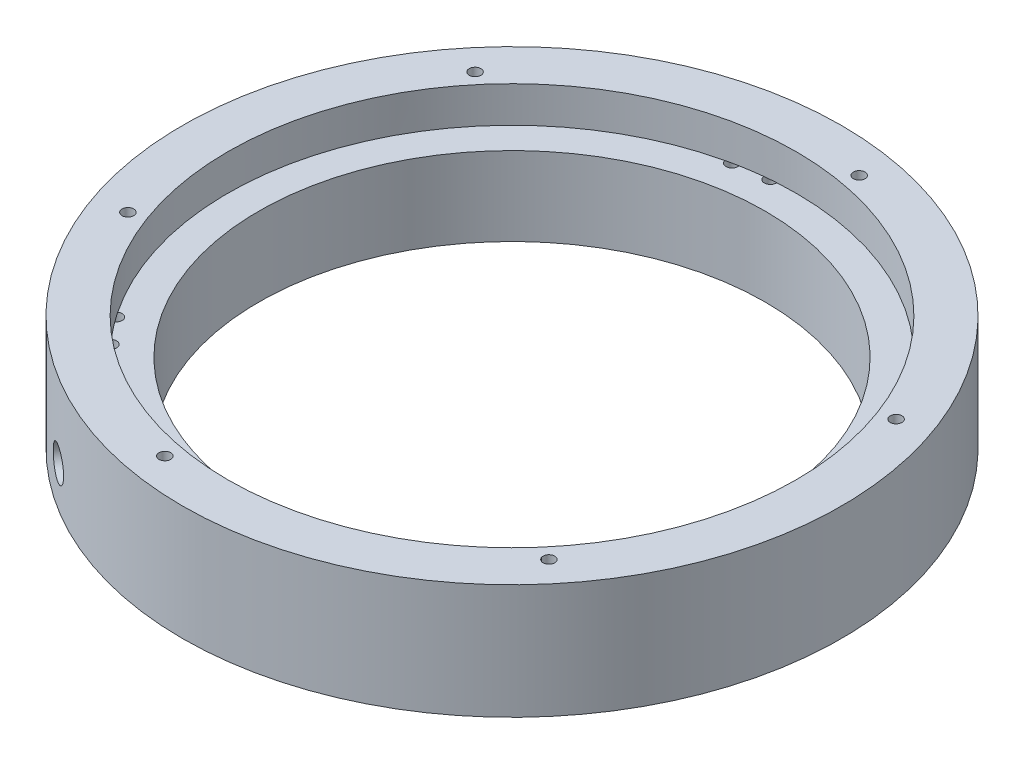
SolidWorks part; units mm, degrees
material "6061 Alloy"
ref_plane "Front Plane" through (0, 0, 0) normal (0, 0, 1) x (1, 0, 0)
ref_plane "Top Plane" through (0, 0, 0) normal (0, 1, 0) x (1, 0, 0)
ref_plane "Right Plane" through (0, 0, 0) normal (1, 0, 0) x (0, 0, -1)
sketch "Sketch1" plane through (0, 0, 0) normal (0, 1, 0) x (1, 0, 0)
  line L0 (26.7963, -63.1282) -> (0, 0) construction
  line L1 (0, 0) -> (0, -32.7983) construction
  line L2 (0, 0) -> (58.126, -27.1046) construction
  line L3 (0, 0) -> (-15.1655, -86.0079) construction
  line L4 (0, 0) -> (84.7676, -52.9687) construction
  circle A0 centre (0, 0) radius 57.15
  circle A1 centre (0, 0) radius 74.3712
  circle A3 centre (0, 0) radius 64.135
  circle A4 centre (-11.7434, -66.6001) radius 1.3208
  circle A5 centre (26.7963, -63.1282) radius 1.9939
  circle A6 centre (26.7963, -63.1282) radius 5.3277
  circle A7 centre (58.126, -27.1046) radius 1.3589
  circle A8 centre (60.9305, -20.0194) radius 1.3589
  dimension "D1" = 114.3
  dimension "D5" = 2.6416
  dimension "D7" = 3.9878
  dimension "D9" = 10.6553
  dimension "D10" = 2.7178
  dimension "D2" = 148.7424
  dimension "D4" = 67.6275
  dimension "D6" = 68.58
  dimension "D8" = 23
  dimension "D11" = 65
  dimension "D15" = 58
  dimension "D12" = 7.62
  dimension "D13" = 10
  dimension "D3" = 6.985
extrude "Boss-Extrude1" add sketch "Sketch1" along normal blind 17.78 contours A7 A3 A6 A0 | A3 A6 A5 | A5 | A3 A6 | A1 A7 A3 A6 A4 | A3 A7 | A3 A7 | A3 A8 | A3 A8 region at (-72.2677, 0, 0) region at (61.6385, 0, 9.1979) region at (24.9157, 0, 58.6977) region at (25.1182, 0, 59.1748) region at (61.4759, 0, 20.1987) region at (60.3801, 0, 19.8386) region at (57.601, 0, 26.8598) region at (58.6464, 0, 27.3473) region at (26.7963, 0, 63.1282)
extrude "Boss-Extrude3" add sketch "Sketch1<3>" along normal blind 8.128 from surface contours A1 A7 A3 A6 A4 | A3 A6 A5 | A5 | A3 A7 | A3 A8 region at (-72.2677, 0, 0) region at (25.1182, 0, 59.1748) region at (61.4759, 0, 20.1987) region at (58.6464, 0, 27.3473) region at (26.7963, 0, 63.1282) starting at face at (0, 17.78, 57.15)
sketch "Sketch1<3>" plane through (0, 0, 0) normal (0, 1, 0) x (1, 0, 0) same geometry as "Sketch1"
pattern_circular "CirPattern1" count 6 over 360 about axis through (0, 25.908, 0) along (0, 1, 0) of face at (-11.7434, 0, 67.9209)
sketch "Sketch2" plane through (0, 0, 0) normal (1, 0, 0) x (0, 0, -1)
  line L0 (-57.15, 0) -> (57.15, 0) construction
  line L1 (57.15, 17.78) -> (-57.15, 17.78) construction
  line L2 (-57.15, 0) -> (57.15, 0)
  line L3 (57.15, 17.78) -> (-57.15, 17.78)
  line L4 (91.6697, 17.018) -> (97.1828, 17.018) construction
  line L5 (0, 17.78) -> (0, 35.8369)
  circle A0 centre (60.6425, 18.6055) radius 1.5875 construction
  circle A1 centre (60.6425, 18.669) radius 1.651
  dimension "D2" = 3.175
  dimension "D4" = 3.302
  dimension "D1" = 60.6425
  dimension "D3" = 0.762
extrude "Cut-Extrude2" cut sketch "Sketch1<4>" along normal blind 5.08 contours A3 A6 A5 | A3 A6 | A6 region at (24.9157, 0, 58.6977) region at (25.1182, 0, 59.1748)
sketch "Sketch1<4>" plane through (0, 0, 0) normal (0, 1, 0) x (1, 0, 0) same geometry as "Sketch1"
extrude "Cut-Extrude3" cut sketch "Sketch1<5>" along normal blind 17.78 contours A5 region at (26.7963, 0, 63.1282)
sketch "Sketch1<5>" plane through (0, 0, 0) normal (0, 1, 0) x (1, 0, 0) same geometry as "Sketch1"
pattern_circular "CirPattern3" count 3 over 360 about axis through (0, 0, 0) along (0, 1, 0) of face at (26.7963, 17.78, 65.1221) of face at (26.7963, 17.78, 65.1221) of face at (26.7963, 5.08, 65.1221) of face at (26.7963, 5.08, 68.4559)
ref_plane "Plane1" through (0, 0, 0) normal (-0.5299, 0, 0.848) x (0.848, 0, 0.5299)
sketch "Sketch3" plane through (0, 0, 0) normal (-0.5299, 0, 0.848) x (0.848, 0, 0.5299)
  line L0 (57.15, 17.78) -> (-57.15, 17.78) construction
  line L1 (57.15, 17.78) -> (-57.15, 17.78)
  line L2 (0, 0) -> (0, 17.78) construction
  circle A0 centre (0, 8.89) radius 3.6576
  circle A1 centre (0, 8.89) radius 3.9751
  dimension "D1" = 7.3152
  dimension "D3" = 7.9502
  dimension "D2" = 8.89
extrude "Cut-Extrude5" cut sketch "Sketch3" along normal up to surface (74.2812 mm away) contours L2 A0 | A0 L2 region at (-1.3165, 8.89, -0.8226) region at (1.3165, 8.89, 0.8226) up to face at (0, 0, 74.3712)
extrude "Cut-Extrude13" cut sketch "Sketch1<6>" along normal up to surface (17.78 mm away) contours A3 A8 | A3 A8 | A7 region at (61.4759, 0, 20.1987) region at (60.3801, 0, 19.8386) up to face at (0, 17.78, 57.15)
sketch "Sketch1<6>" plane through (0, 0, 0) normal (0, 1, 0) x (1, 0, 0) same geometry as "Sketch1"
pattern_circular "CirPattern4" count 3 over 360 about axis through (0, 0, 0) along (0, 1, 0) of "Cut-Extrude13"
equation "\"Middle Coupler Inner Daimeter\"= 3.875in"
equation "\"Middle Coupler  Wall Thickness\" = 0.25in"
equation "\"Middle Coupler Bottom Thickness\"= 0.2in"
equation "\"Bearing Rail Offset\"= 0.45in"
equation "\"3-56 UNF Tap\"= 0.089in"
equation "\"3-56 UNF Clearance\"= 0.104in"
equation "\"Ball Bearing Distance\"= 0.03in"
equation "\"D1@Sketch1\"=\"Middle Coupler Inner Daimeter\"+0.625in"
equation "\"D3@Sketch1\"=0.275"
equation "\"D4@Sketch1\"=\"Middle Coupler Inner Daimeter\"/2+0.625/2+0.275+0.275/2"
equation "\"D5@Sketch1\"=\"3-48 Clearance\""
equation "\"D1@Sketch2\"=\"Middle Coupler Inner Daimeter\"/2in + \"Bearing Rail Offset\""
equation "\"D3@Sketch2\"=\"Ball Bearing Distance\""
equation "\"D4@Sketch2\"=\"D2@Sketch2\"+0.005"
equation "\"D1@Boss-Extrude3\"=0.3 + 0.01*2"
equation "\"TCA Outer Diameter\" = 6in"
equation "\"Interstage Aeroframe Wall Thickness\" = 0.072in"
equation "\"Compression Spring OD\"= 0.42in"
equation "\"10-24 Tap\"= 0.157in"
equation "\"10-24 Clearance\"= 0.196in"
equation "\"Lower Stage Fuselage Wall Thickness\" = 0.25in"
equation "\"6-32 Tap\" = 0.107in"
equation "\"D10@Sketch1\"=\"6-32 Tap\""
equation "\"1/4-20 Tap\" = 0.201in"
equation "\"D1@Sketch3\"=0.176 + 0.056*2"
equation "\"12-24 Tap\" = 0.177in"
equation "\"D3@Sketch3\"=0.313"
equation "\"3-48 Tap\"= 0.079in"
equation "\"3-48 Clearance\" = 0.104in"
equation "\"6-32 Clearance\" = 0.144"
equation "\"D2@Sketch1\"=\"TCA Outer Diameter\"-\"Interstage Aeroframe Wall Thickness\"*2"
equation "\"D6@Sketch1\"=(\"Middle Coupler Inner Daimeter\"+\"TCA Outer Diameter\"+0.5+0.0125*2in)/4 + 0.1"
equation "\"D1@Cut-Extrude3\"=0.2 + 0.5"
